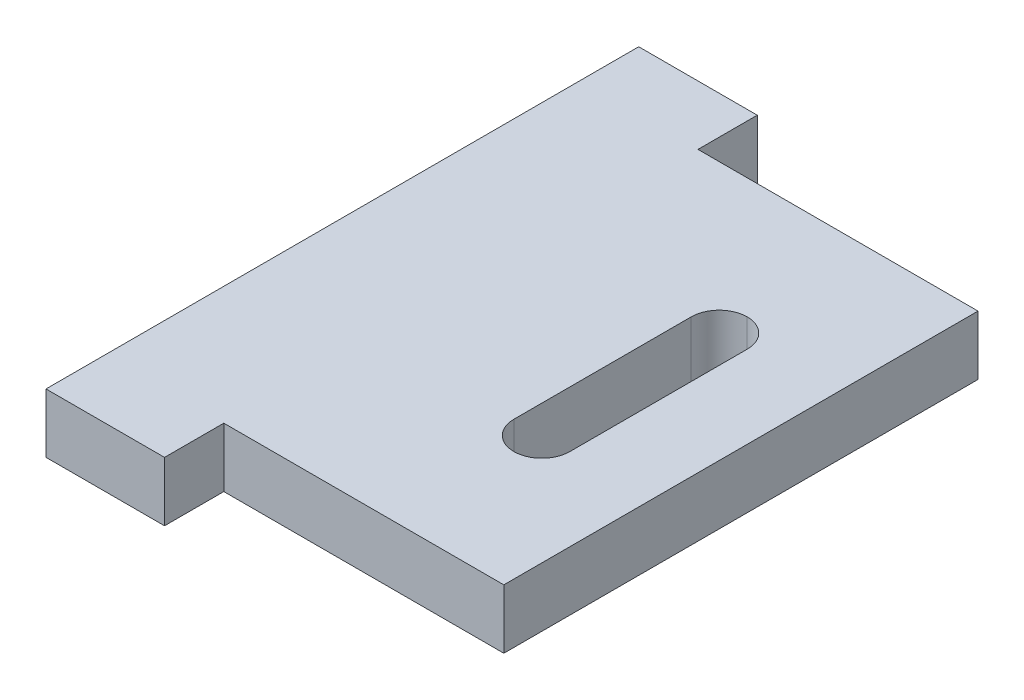
SolidWorks part; units mm, degrees
material "Maple"
ref_plane "Front Plane" through (0, 0, 0) normal (0, 0, 1) x (1, 0, 0)
ref_plane "Top Plane" through (0, 0, 0) normal (0, 1, 0) x (1, 0, 0)
ref_plane "Right Plane" through (0, 0, 0) normal (1, 0, 0) x (0, 0, -1)
sketch "Sketch1" plane through (0, 0, 0) normal (0, 1, 0) x (1, 0, 0)
  line L1 (-7.5, 12.7) -> (7.5, 12.7)
  line L2 (-7.5, 12.7) -> (-7.5, -12.7)
  line L3 (-7.5, -12.7) -> (7.5, -12.7)
  line L4 (7.5, 12.7) -> (7.5, -12.7)
  line L5 (0, -12.7) -> (0, 12.7) construction
  line L6 (-7.5, 0) -> (7.5, 0) construction
  line L7 (-13.85, 15.875) -> (-7.5, 15.875)
  line L8 (-13.85, 15.875) -> (-13.85, -15.875)
  line L9 (-13.85, -15.875) -> (-7.5, -15.875)
  line L10 (-7.5, 15.875) -> (-7.5, -15.875)
  line L11 (-10.675, -15.875) -> (-10.675, 15.875) construction
  line L12 (-13.85, 0) -> (-7.5, 0) construction
  point P0 (0, 0)
  point P4 (-10.675, 0)
  dimension "D1" = 25.4
  dimension "D2" = 15
  dimension "D3" = 6.35
  dimension "D4" = 31.75
extrude "Boss-Extrude1" add sketch "Sketch1" along normal blind 3.175 contours L10 L7 L8 L9 L2 | L4 L1 L2 L3 region at (0, 0, 0) region at (-10.675, 0, 0)
sketch "Sketch2" plane through (0, 3.175, 0) normal (0, 1, 0) x (1, 0, 0)
  line L0 (-7.5, 0) -> (7.5, 0) construction
  line L1 (3.0875, 6.25) -> (0.0875, 6.25)
  line L2 (3.0875, 6.25) -> (3.0875, -6.25)
  line L3 (3.0875, -6.25) -> (0.0875, -6.25)
  line L4 (0.0875, 6.25) -> (0.0875, -6.25)
  line L5 (1.5875, -6.25) -> (1.5875, 6.25) construction
  line L6 (3.0875, 0) -> (0.0875, 0) construction
  line L7 (-4.325, 10.924) -> (-4.325, -49989.076) construction
  line L8 (-7.5, 15.875) -> (-7.5, -15.875) construction
  line L9 (0.0875, 0) -> (-4.325, 0) construction
  line L10 (3.0875, 0) -> (7.5, 0) construction
  point P0 (1.5875, 0)
  dimension "D1" = 3.175
  dimension "D2" = 3
  dimension "D3" = 12.5
extrude "Cut-Extrude1" cut sketch "Sketch2" against normal through all both and the other way through all
fillet "Fillet1" radius 1.5 4 edges at (3.0875, 1.5875, -6.25) (3.0875, 1.5875, 6.25) (0.0875, 1.5875, 6.25) (0.0875, 1.5875, -6.25)
